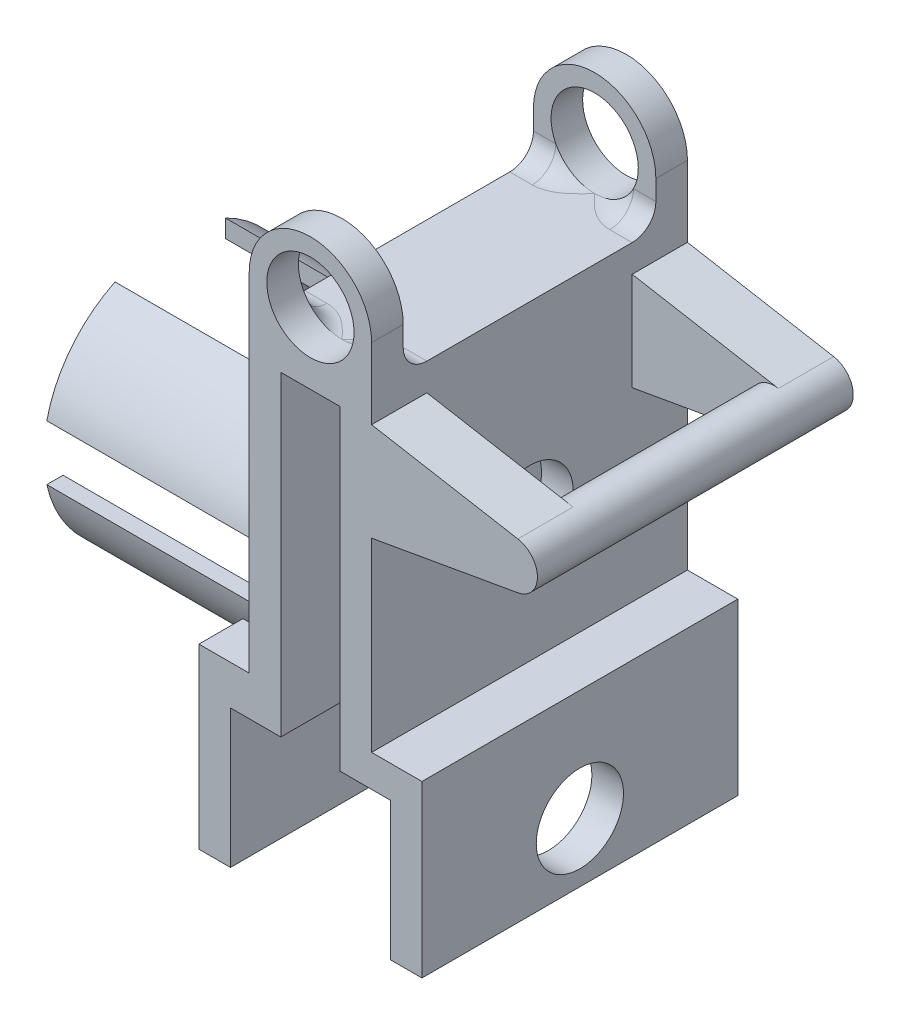
SolidWorks part; units mm, degrees
material "Custom Plastic"
ref_plane "Front Plane" through (0, 0, 0) normal (0, 0, 1) x (1, 0, 0)
ref_plane "Top Plane" through (0, 0, 0) normal (0, 1, 0) x (1, 0, 0)
ref_plane "Right Plane" through (0, 0, 0) normal (1, 0, 0) x (0, 0, -1)
sketch "Sketch1" plane through (0, 0, 0) normal (0, 0, 1) x (1, 0, 0)
  line L0 (0, 0) -> (0, 40)
  line L1 (0, 40) -> (7.5, 40)
  line L2 (7.5, 40) -> (7.5, 0)
  line L3 (7.5, 0) -> (13.875, 0)
  line L7 (15.875, 4.0578) -> (13.5, 4.0578)
  line L8 (11.5, 6.0578) -> (11.5, 27.5597)
  line L10 (-4, 37.9136) -> (-4, 7)
  line L11 (-6, 5) -> (-8.375, 5)
  line L15 (-6.375, 0) -> (0, 0)
  line L16 (-6.375, 0) -> (-6.375, -17.5)
  line L17 (-10.375, 3) -> (-10.375, -17.5)
  line L18 (-10.375, -17.5) -> (-6.375, -17.5)
  line L19 (13.875, 0) -> (13.875, -17.5)
  line L20 (13.875, -17.5) -> (17.875, -17.5)
  line L21 (17.875, -17.5) -> (17.875, 2.0578)
  line L22 (-10.375, 3) -> (-10.375, 5)
  line L23 (-10.375, 5) -> (-8.375, 5)
  line L24 (-6, 5) -> (-4, 5)
  line L25 (-4, 5) -> (-4, 7)
  line L26 (11.5, 6.0578) -> (11.5, 4.0578)
  line L27 (11.5, 4.0578) -> (13.5, 4.0578)
  line L28 (15.875, 4.0578) -> (17.875, 4.0578)
  line L29 (17.875, 4.0578) -> (17.875, 2.0578)
  line L32 (11.5, 40) -> (0, 40) construction
  line L36 (-4, 37.9136) -> (-4, 49)
  line L37 (-4, 49) -> (11.5, 49) construction
  line L38 (11.5, 40) -> (30.0209, 36.7343)
  line L39 (30.0209, 36.7343) -> (30.0209, 30.8254) construction
  line L40 (30.0209, 30.8254) -> (11.5, 27.5597)
  line L41 (11.5, 40) -> (11.5, 49)
  circle A5 centre (3.75, 49) radius 5.525
  arc A6 (11.5, 49) -> (-4, 49) centre (3.75, 49) ccw
  arc A7 (30.0209, 30.8254) -> (30.0209, 36.7343) centre (29.5, 33.7798) ccw
  point P30 (-10.375, 5)
  dimension "D9" = 18
  dimension "D5" = 11.05
  dimension "D6" = 9
  dimension "D7" = 3
  dimension "D1" = 7.5
  dimension "D2" = 40
  dimension "D3" = 20.25
  dimension "D4" = 17.5
  dimension "D8" = 100
  dimension "D10" = 4
  dimension "D11" = 4
extrude "Boss-Extrude1" add sketch "Sketch1" along normal blind 40
sketch "Sketch2" plane through (-4, 0, 0) normal (-1, 0, 0) x (0, 0, 1)
  line L0 (0, 49) -> (0, 5) construction
  line L1 (40, 0) -> (0, 0) construction
  circle A0 centre (20, 20) radius 5.525
  dimension "D1" = 11.05
  dimension "D3" = 20
  dimension "D2" = 20
extrude "Cut-Extrude1" cut sketch "Sketch2" against normal up to surface (15.5 mm away) contours A0 up to face at (11.5, 15.8087, 20)
sketch "Sketch3" plane through (-10.375, 0, 0) normal (-1, 0, 0) x (0, 0, 1)
  line L0 (40, 0) -> (0, 0) construction
  line L1 (40, 5) -> (40, -17.5) construction
  circle A0 centre (20, -10) radius 5.525
  dimension "D1" = 11.05
  dimension "D2" = 10
extrude "Cut-Extrude2" cut sketch "Sketch3" against normal blind 124.5 contours A0
sketch "Sketch5" plane through (-4, 0, 0) normal (-1, 0, 0) x (0, 0, 1)
  line L5 (20, 20) -> (20, 28)
  line L6 (2.5, 31.5) -> (6.4446, 31.5)
  line L7 (2.5, 24.5) -> (6.4446, 24.5)
  line L8 (37.5, 31.5) -> (33.5554, 31.5)
  line L9 (33.5554, 24.5) -> (37.5, 24.5)
  line L11 (13, 45) -> (27, 45)
  line L12 (13, 45) -> (13, 40.1244)
  line L14 (27, 45) -> (27, 40.1244)
  circle A1 centre (20, 20) radius 2.5
  arc A2 (6.4446, 24.5) -> (33.5554, 24.5) centre (20, 28) ccw
  arc A4 (2.5, 31.5) -> (2.5, 24.5) centre (2.5, 28) ccw
  arc A5 (37.5, 24.5) -> (37.5, 31.5) centre (37.5, 28) ccw
  arc A6 (33.5554, 31.5) -> (27, 40.1244) centre (20, 28) ccw
  circle A7 centre (2.5, 28) radius 2.1
  circle A8 centre (37.5, 28) radius 2.1
  arc A9 (13, 40.1244) -> (6.4446, 31.5) centre (20, 28) ccw
  point P0 (20, 20)
  dimension "D2" = 8
  dimension "D1" = 5
  dimension "D3" = 28
  dimension "D4" = 4.2
  dimension "D5" = 7
  dimension "D6" = 7
  dimension "D7" = 4.2
  dimension "D9" = 14
sketch "Sketch7" plane through (-4, 0, 0) normal (-1, 0, 0) x (0, 0, 1)
  line L1 (13, -0.1532) -> (13, -2.4153)
  line L3 (13, 26.4153) -> (13, 24.1532)
  line L5 (27, 26.4153) -> (27, 24.1532)
  line L6 (33.5813, 15.5) -> (35.6381, 15.5)
  line L7 (4.3619, 15.5) -> (6.4187, 15.5)
  line L9 (4.3619, 8.5) -> (6.4187, 8.5)
  line L10 (27, -0.1532) -> (27, -2.4153)
  line L12 (33.5813, 8.5) -> (35.6381, 8.5)
  arc A0 (27, -0.1532) -> (33.5813, 8.5) centre (20, 12) ccw
  arc A1 (27, -2.4153) -> (35.6381, 8.5) centre (20, 12) ccw
  circle A2 centre (20, 12) radius 14.025 construction
  circle A3 centre (20, 12) radius 16.025 construction
  arc A4 (13, 24.1532) -> (6.4187, 15.5) centre (20, 12) ccw
  arc A5 (13, 26.4153) -> (4.3619, 15.5) centre (20, 12) ccw
  arc A6 (4.3619, 8.5) -> (13, -2.4153) centre (20, 12) ccw
  arc A7 (6.4187, 8.5) -> (13, -0.1532) centre (20, 12) ccw
  arc A8 (33.5813, 15.5) -> (27, 24.1532) centre (20, 12) ccw
  arc A9 (35.6381, 15.5) -> (27, 26.4153) centre (20, 12) ccw
  dimension "D2" = 28.05
  dimension "D3" = 2
extrude "Boss-Extrude2" add sketch "Sketch7" along normal blind 30 contours L6 A9 L5 A8 | A5 L7 A4 L3 | A1 L12 A0 L10 | A6 L1 A7 L9 region at (-4, 20.9711, 31.536)
sketch "Sketch8" plane through (0, 0, 0) normal (0, 0, -1) x (-1, 0, 0)
  line L1 (6.375, 0) -> (0, 0)
  line L2 (6.375, 0) -> (6.375, -4.2523)
  line L3 (6.375, -4.2523) -> (0, -4.2523)
  line L4 (0, 0) -> (0, -4.2523)
extrude "Cut-Extrude4" cut sketch "Sketch8" against normal blind 54
sketch "Sketch12" plane through (-4, 0, 0) normal (-1, 0, 0) x (0, 0, 1)
  line L0 (40, 56.75) -> (0, 56.75) construction
  line L1 (4, 70.025) -> (36, 70.025)
  line L2 (4, 70.025) -> (4, 43.475)
  line L3 (4, 43.475) -> (36, 43.475)
  line L4 (36, 70.025) -> (36, 43.475)
  line L5 (4, 70.025) -> (36, 43.475) construction
  line L6 (4, 43.475) -> (36, 70.025) construction
  line L7 (0, 49) -> (0, 5) construction
  point P0 (20, 56.75)
  dimension "D1" = 4
extrude "Cut-Extrude6" cut sketch "Sketch12" against normal blind 56 contours L1 L4 L3 L2
fillet "Fillet2" radius 3 4 edges at (7.625, 43.475, 36) (7.625, 43.475, 4) (-0.125, 43.475, 4) (-0.125, 43.475, 36)
sketch "Sketch13" plane through (0, 43.475, 0) normal (0, 1, 0) x (1, 0, 0)
  line L0 (11.5, -33) -> (41.4726, -33)
  line L1 (11.5, -40) -> (11.5, 0) construction
  line L2 (41.4726, -33) -> (41.5699, -7)
  line L4 (41.5699, -7) -> (11.5, -7)
  line L5 (11.5, -7) -> (11.5, -33) construction
  line L6 (11.5, -7) -> (11.5, -33)
  line L8 (30.0209, -40) -> (11.5, -40) construction
  line L9 (30.0209, 0) -> (11.5, 0) construction
  line L10 (11.5, -7) -> (11.5, -4) construction
  dimension "D1" = 7
  dimension "D2" = 7
extrude "Cut-Extrude9" cut sketch "Sketch13" against normal blind 24 contours L4 L6 L0 L2
sketch "Sketch14" plane through (0, 0, 33) normal (0, 0, -1) x (-1, 0, 0)
  circle A0 centre (-29.5, 33.7798) radius 3
  arc A1 (-30.0209, 36.7343) -> (-30.0209, 30.8254) centre (-29.5, 33.7798) ccw construction
extrude "Boss-Extrude4" add sketch "Sketch14" along normal up to surface (26 mm away) contours A0 up to face at (21.3802, 33.7798, 7)
